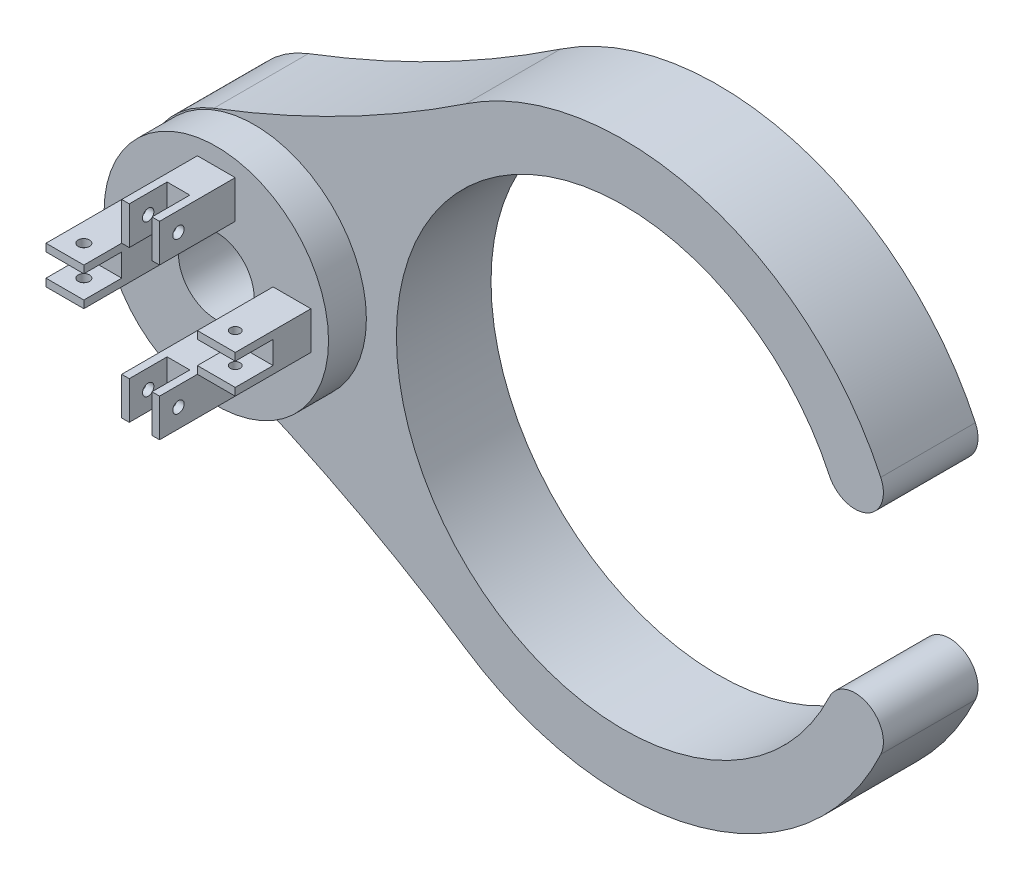
SolidWorks part; units mm, degrees
ref_plane "Front Plane" through (0, 0, 0) normal (0, 0, 1) x (1, 0, 0)
ref_plane "Top Plane" through (0, 0, 0) normal (0, 1, 0) x (1, 0, 0)
ref_plane "Right Plane" through (0, 0, 0) normal (1, 0, 0) x (0, 0, -1)
sketch "Sketch1" plane through (0, 0, 0) normal (0, 0, 1) x (1, 0, 0)
  line L0 (34.474, 150) -> (149.7758, 8.1988) construction
  line L5 (149.7758, 8.1988) -> (150.0785, 7.9686) construction
  line L6 (184.474, 150) -> (0, 0) construction
  line L7 (146.6155, 100.3571) -> (160.2101, 106.6964) construction
  line L8 (146.6155, 49.6429) -> (160.2101, 43.3036) construction
  arc A0 (50.6007, 12.6188) -> (160.2101, 43.3036) centre (92.237, 75) ccw
  arc A1 (-16.0106, 103.0401) -> (-16.0106, 46.9599) centre (-5.345, 75) ccw
  arc A2 (-16.0106, 103.0401) -> (50.6007, 137.3812) centre (-134.6377, 414.9134) ccw
  arc A3 (50.6007, 12.6188) -> (-16.0106, 46.9599) centre (-134.6377, -264.9134) ccw
  arc A4 (146.6155, 100.3571) -> (146.6155, 49.6429) centre (92.237, 75) ccw
  arc A5 (160.2101, 106.6964) -> (146.6155, 100.3571) centre (153.4128, 103.5267) cw
  arc A6 (160.2101, 43.3036) -> (146.6155, 49.6429) centre (153.4128, 46.4733) ccw
  arc A7 (160.2101, 106.6964) -> (50.6007, 137.3812) centre (92.237, 75) ccw
  circle A8 centre (-5.345, 75) radius 29.652
  point P9 (-35.345, 75)
  dimension "D1" = 150
  dimension "D3" = 150
  dimension "D4" = 120
  dimension "D5" = 30
  dimension "D2" = 145.9847
  dimension "D8" = 50
  dimension "D9" = 150
  dimension "D10" = 0
extrude "Boss-Extrude1" add sketch "Sketch1" along normal blind 25 contours A1 A3 A0 A6 A4 A5 A7 A2 | A8 region at (19.3942, 33.8609, 0) region at (-5.345, 75, 0)
extrude "Boss-Extrude2" add sketch "Sketch1<3>" along normal blind 35 contours A8
sketch "Sketch1<3>" plane through (0, 0, 0) normal (0, 0, 1) x (1, 0, 0) same geometry as "Sketch1"
sketch "Sketch3" plane through (0, 0, 35) normal (0, 0, 1) x (1, 0, 0)
  circle A0 centre (-5.345, 75) radius 10
extrude "Cut-Extrude1" cut sketch "Sketch3" against normal blind 35
sketch "Sketch4" plane through (0, 0, 35) normal (0, 0, 1) x (1, 0, 0)
  line L0 (19.655, 70) -> (19.655, 80)
  line L1 (9.655, 70) -> (19.655, 70)
  line L2 (9.655, 70) -> (9.655, 80)
  line L3 (9.655, 80) -> (19.655, 80)
  line L4 (-10.345, 50) -> (-0.345, 50)
  line L5 (-10.345, 60) -> (-10.345, 50)
  line L6 (-10.345, 60) -> (-0.345, 60)
  line L7 (-0.345, 90) -> (-10.345, 90)
  line L8 (-0.345, 90) -> (-0.345, 100)
  line L9 (-0.345, 100) -> (-10.345, 100)
  line L10 (-10.345, 90) -> (-10.345, 100)
  line L11 (-0.345, 90) -> (-10.345, 100) construction
  line L12 (-0.345, 100) -> (-10.345, 90) construction
  line L13 (-0.345, 60) -> (-0.345, 50)
  line L14 (-30.345, 80) -> (-30.345, 70)
  line L15 (-20.345, 80) -> (-30.345, 80)
  line L16 (-20.345, 80) -> (-20.345, 70)
  line L17 (-20.345, 70) -> (-30.345, 70)
  line L31 (-10.345, 90) -> (-5.345, 95) construction
  point P0 (-5.345, 75)
  point P21 (-5.345, 75)
  dimension "D1" = 0
  dimension "D2" = 4
  dimension "D3" = 20
extrude "Boss-Extrude3" add sketch "Sketch4" along normal blind 20
sketch "Sketch5" plane through (0, 0, 55) normal (0, 0, 1) x (1, 0, 0)
  line L0 (-0.345, 100) -> (-10.345, 100) construction
  line L1 (-2.345, 100) -> (-8.345, 100)
  line L2 (-2.345, 100) -> (-2.345, 90)
  line L3 (-2.345, 90) -> (-8.345, 90)
  line L4 (-8.345, 100) -> (-8.345, 90)
  line L5 (-10.345, 90) -> (-0.345, 90) construction
  line L6 (-10.345, 100) -> (-10.345, 90) construction
  line L7 (-2.345, 100) -> (-8.345, 90) construction
  line L8 (-8.345, 100) -> (-2.345, 90) construction
  line L9 (-2.345, 90) -> (-2.8332, 90.3475) construction
  line L10 (19.655, 72) -> (19.655, 78)
  line L11 (19.655, 72) -> (9.655, 72)
  line L12 (9.655, 72) -> (9.655, 78)
  line L13 (19.655, 78) -> (9.655, 78)
  line L14 (9.655, 72) -> (10.0025, 72.4882) construction
  line L15 (-8.345, 50) -> (-2.345, 50)
  line L16 (-8.345, 50) -> (-8.345, 60)
  line L17 (-8.345, 60) -> (-2.345, 60)
  line L18 (-2.345, 50) -> (-2.345, 60)
  line L19 (-8.345, 60) -> (-7.8568, 59.6525) construction
  line L20 (-30.345, 78) -> (-30.345, 72)
  line L21 (-30.345, 78) -> (-20.345, 78)
  line L22 (-20.345, 78) -> (-20.345, 72)
  line L23 (-30.345, 72) -> (-20.345, 72)
  line L24 (-20.345, 78) -> (-20.6925, 77.5118) construction
  point P4 (-5.345, 95)
  point P30 (-5.345, 75)
  dimension "D1" = 6
  dimension "D2" = 2
  dimension "D3" = 4
extrude "Cut-Extrude2" cut sketch "Sketch5" against normal blind 10
sketch "Sketch6" plane through (0, 70, 0) normal (0, -1, 0) x (-1, 0, 0)
  line L0 (-9.655, -55) -> (-19.655, -55) construction
  line L1 (30.345, -55) -> (20.345, -55) construction
  circle A0 centre (-14.655, -50) radius 1.3
  circle A1 centre (25.345, -50) radius 1.5
  dimension "D1" = 5
  dimension "D2" = 5
extrude "Cut-Extrude3" cut sketch "Sketch6" against normal blind 10
sketch "Sketch7" plane through (-10.345, 0, 0) normal (-1, 0, 0) x (0, 0, 1)
  line L0 (55, 60) -> (55, 50) construction
  line L1 (55, 100) -> (55, 90) construction
  circle A0 centre (50, 55) radius 1.5
  circle A1 centre (50, 95) radius 1.5
  point P4 (0, 0)
  dimension "D1" = 5
  dimension "D2" = 5
extrude "Cut-Extrude4" cut sketch "Sketch7" against normal blind 10
